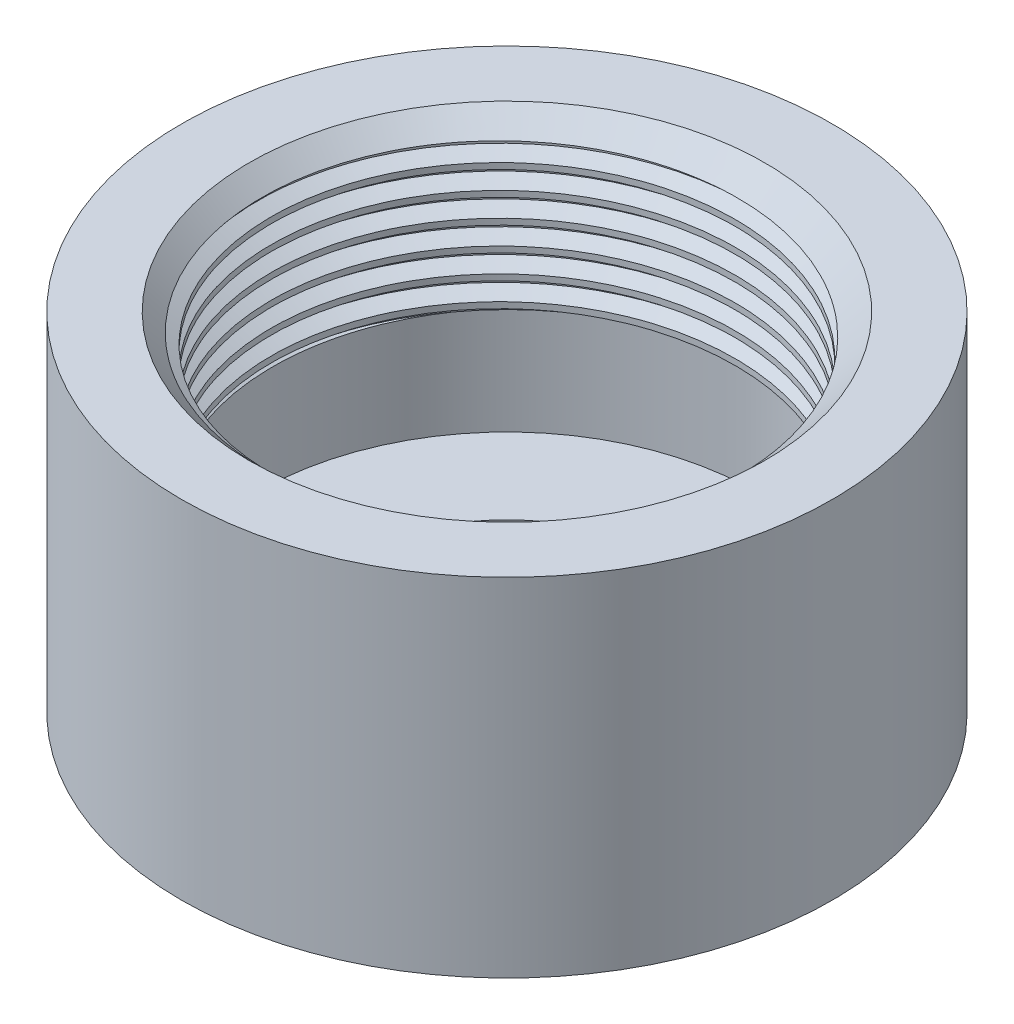
SolidWorks part; units mm, degrees
ref_plane "Front Plane" through (0, 0, 0) normal (0, 0, 1) x (1, 0, 0)
ref_plane "Top Plane" through (0, 0, 0) normal (0, 1, 0) x (1, 0, 0)
ref_plane "Right Plane" through (0, 0, 0) normal (1, 0, 0) x (0, 0, -1)
sketch "Sketch1" plane through (0, 0, 0) normal (0, 0, 1) x (1, 0, 0)
  line L0 (0, 17.6089) -> (0, -7.0755) construction
  line L1 (8.255, 0) -> (19.05, 0)
  line L2 (19.05, 0) -> (19.05, 20.32)
  line L3 (19.05, 20.32) -> (15.1003, 20.32)
  line L5 (13.5763, 18.796) -> (13.5763, 10.287)
  line L6 (13.5763, 10.287) -> (14.5415, 10.287)
  line L7 (14.5415, 10.287) -> (14.5415, 3.937)
  line L8 (14.5415, 3.937) -> (8.255, 3.937)
  line L9 (8.255, 3.937) -> (8.255, 0)
  line L10 (15.1003, 20.32) -> (13.5763, 18.796)
  point P5 (14.5415, 7.112)
  point P13 (13.5763, 20.32)
  dimension "D1" = 38.1
  dimension "D2" = 27.1526
  dimension "D3" = 29.083
  dimension "D4" = 16.383
  dimension "D5" = 20.32
  dimension "D6" = 16.51
  dimension "D7" = 6.35
revolve "Revolve1" add sketch "Sketch1" angle 360 about L0
thread "Thread1" pitch 1.4111 start angle 0, offset 3.54, length 0, pitch 1.4111, diameter 27.1526
ref_plane "Plane2" through (-13.5763, 22.336, 0) normal (0, 0, 1) x (-1, 0, 0)
sketch "Thread Profile2" plane through (-13.5763, 22.336, 0) normal (0, 0, 1) x (-1, 0, 0)
  line L0 (0, 0) -> (0, 1.4111) construction
  line L1 (0, 0) -> (0.7638, 0.441)
  line L2 (0.7638, 0.441) -> (0.7638, 0.6174)
  line L3 (0.7638, 0.6174) -> (0, 1.0583)
  line L4 (0.7638, 0.5292) -> (0, 0.5292) construction
  line L11 (0, 0) -> (0, 1.0583)
  point P2 (0, 0)
  dimension "Pitch" = 1.4111
  dimension "Profile_Angle" = 60
  dimension "Profile_Land" = 0.1764
  dimension "Profile_Height" = 0.7638
